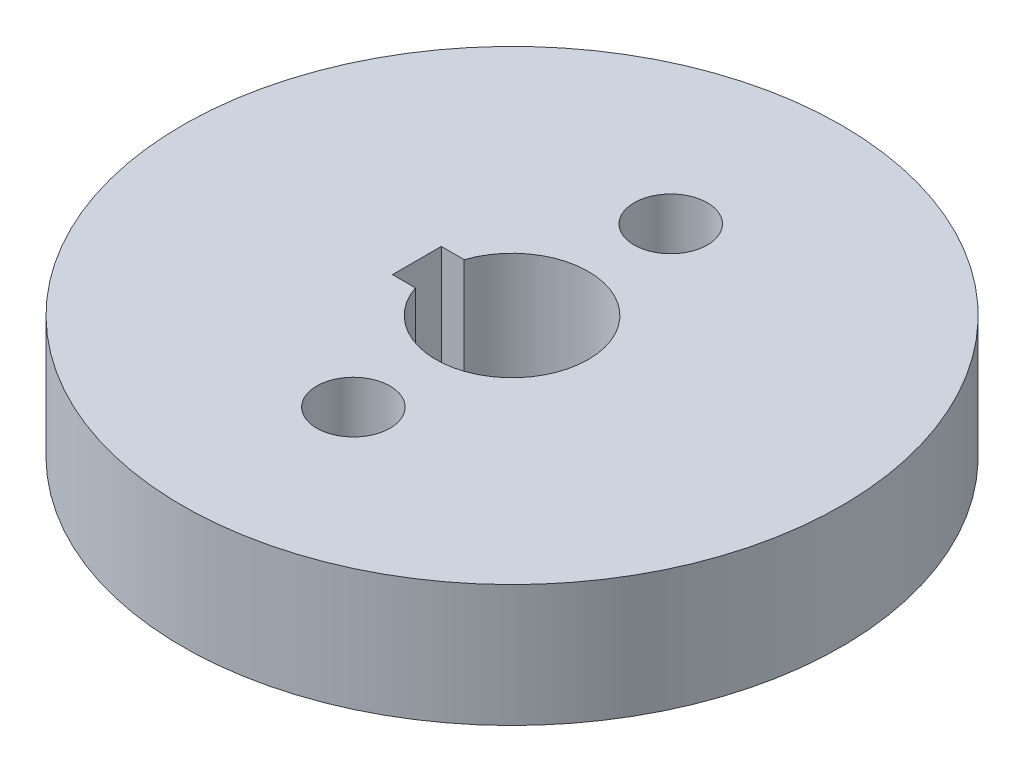
SolidWorks part; units mm, degrees
ref_plane "Спереди" through (0, 0, 0) normal (0, 0, 1) x (1, 0, 0)
ref_plane "Сверху" through (0, 0, 0) normal (0, 1, 0) x (1, 0, 0)
ref_plane "Справа" through (0, 0, 0) normal (1, 0, 0) x (0, 0, -1)
sketch "Эскиз1" plane through (0, 0, 0) normal (0, 0, 1) x (1, 0, 0)
  line L0 (0, 0) -> (0, 20) construction
  line L1 (0, 0) -> (12.5, 0) construction
  line L2 (12.5, 0) -> (12.5, 20)
  line L3 (12.5, 20) -> (0, 20) construction
  line L4 (12.5, 20) -> (54, 20)
  line L5 (54, 20) -> (54, 0)
  line L6 (12.5, 0) -> (54, 0)
  dimension "D1" = 20
  dimension "D2" = 12.5
  dimension "D3" = 54
revolve "Повернуть1" add sketch "Эскиз1" angle 360 about L0
ref_plane "Плоскость1" through (0, 20, 0) normal (0, 1, 0) x (1, 0, 0)
sketch "Эскиз2" plane through (0, 20, 0) normal (0, 1, 0) x (1, 0, 0)
  line L0 (0, 12.5) -> (0, -12.5) construction
  line L1 (-12.5, 0) -> (12.5, 0) construction
  line L2 (-11.8427, 4) -> (-15.6, 4)
  line L3 (-15.6, 4) -> (-15.6, -4)
  line L4 (-15.6, -4) -> (-11.8427, -4)
  line L5 (0, -26) -> (0, 26) construction
  circle A0 centre (0, 0) radius 12.5 construction
  arc A1 (-11.8427, -4) -> (-11.8427, 4) centre (0, 0) ccw
  circle A4 centre (0, 0) radius 26 construction
  circle A5 centre (0, 26) radius 6
  circle A6 centre (0, -26) radius 6
  point P11 (-13.7214, -4)
  point P17 (0, 0)
  dimension "D4" = 52
  dimension "D5" = 12
  dimension "D6" = 12
  dimension "D1" = 28.1
  dimension "D2" = 8
  dimension "D3" = 4
extrude "Вырез-Вытянуть1" cut sketch "Эскиз2" against normal blind 20 contours A5
extrude "Вырез-Вытянуть2" cut sketch "Эскиз2<3>" against normal blind 20
sketch "Эскиз2<3>" plane through (0, 20, 0) normal (0, 1, 0) x (1, 0, 0) same geometry as "Эскиз2"
ref_plane "Плоскость2" through (0, 20, 0) normal (0, 1, 0) x (1, 0, 0)
